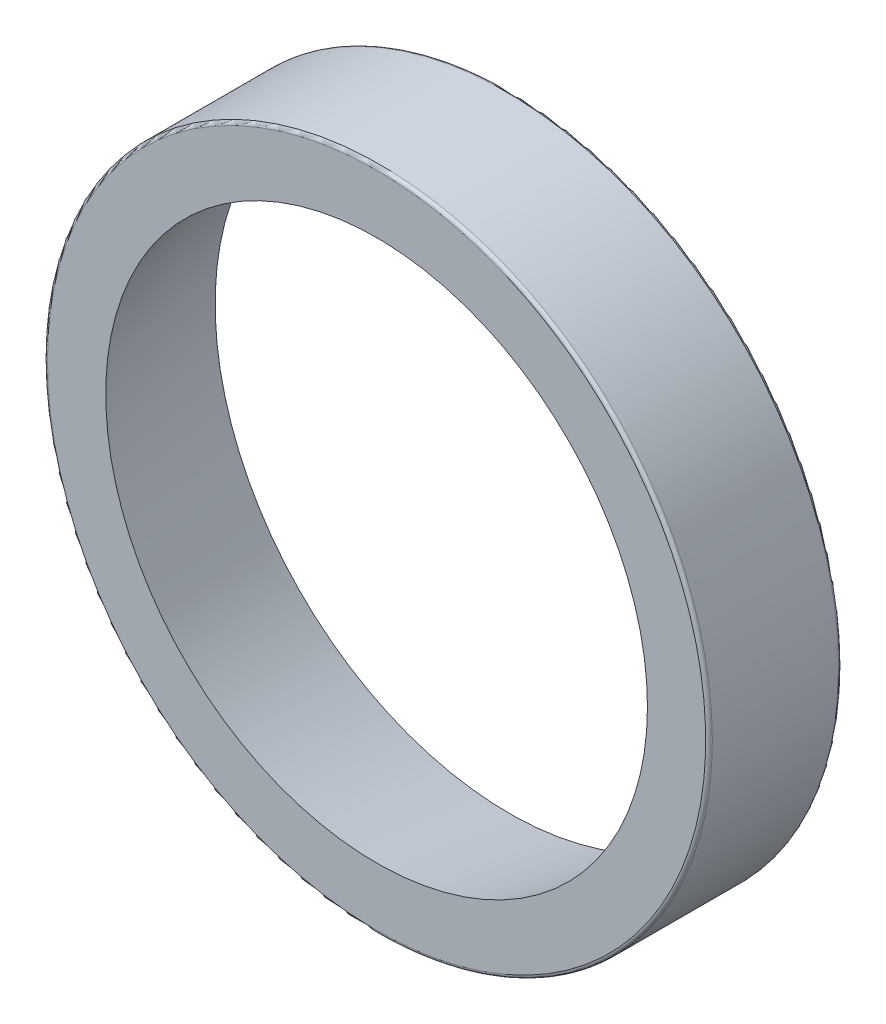
SolidWorks part; units mm, degrees
ref_plane "Front Plane" through (0, 0, 0) normal (0, 0, 1) x (1, 0, 0)
ref_plane "Top Plane" through (0, 0, 0) normal (0, 1, 0) x (1, 0, 0)
ref_plane "Right Plane" through (0, 0, 0) normal (1, 0, 0) x (0, 0, -1)
sketch "Sketch1" plane through (0, 0, 0) normal (1, 0, 0) x (0, 0, -1)
  line L0 (-8.3344, 0) -> (8.3344, 0) construction
  line L1 (0, 0) -> (0, 29.5656) construction
  line L2 (-8.3344, 15.875) -> (8.3344, 15.875) construction
  line L3 (8.3344, 15.875) -> (8.3344, 21.3512) construction
  line L4 (8.3344, 21.3512) -> (-8.3344, 18.4121) construction
  line L5 (-8.3344, 18.4121) -> (-8.3344, 15.875) construction
  line L7 (-8.3344, 29.5656) -> (3.4766, 29.5656)
  line L8 (3.4766, 29.5656) -> (3.4766, 26.172)
  line L9 (3.4766, 26.172) -> (-8.3344, 24.0894)
  line L10 (-8.3344, 24.0894) -> (-8.3344, 29.5656)
  line L11 (-8.3344, 24.0894) -> (-7.3635, 18.5833) construction
  line L12 (6.5698, 26.7174) -> (7.5406, 21.2113) construction
  line L14 (-8.3344, 18.4121) -> (-7.3635, 18.5833) construction
  line L15 (-8.3344, 18.4121) -> (7.5406, 21.2113) construction
  point P5 (0, 15.875)
  dimension "D1" = 100
  dimension "Width" = 16.6687
  dimension "OD" = 59.1312
  dimension "Shaft Dia" = 31.75
  dimension "D2" = 13.6906
  dimension "D3" = 5.4762
  dimension "Outer Wd" = 11.811
  dimension "Bearing Wd" = 15.875
revolve "Revolve1" add sketch "Sketch1" angle 360 about L0
sketch "Sketch5" plane through (0, 0, 0) normal (1, 0, 0) x (0, 0, -1)
  line L0 (8.3344, 21.3512) -> (-8.3344, 18.4121) construction
  line L1 (8.3344, 21.3512) -> (-8.3344, 18.4121)
  line L2 (-8.3344, 18.4121) -> (-8.3344, 15.875)
  line L3 (-8.3344, 15.875) -> (8.3344, 15.875)
  line L4 (8.3344, 15.875) -> (8.3344, 21.3512)
revolve "Revolve4" [suppressed] add sketch "Sketch5" angle 360 about L0
sketch "Sketch2" plane through (0, 0, 0) normal (1, 0, 0) x (0, 0, -1)
  line L0 (-8.3344, 23.3792) -> (-8.3344, 19.1222)
  line L1 (3.4766, 25.4618) -> (6.6912, 26.0286)
  line L2 (-8.3344, 19.1222) -> (3.4766, 21.2048)
  line L3 (6.5698, 26.7174) -> (7.5406, 21.2113) construction
  line L4 (3.4766, 21.2048) -> (3.4766, 25.4618) construction
  line L5 (3.4766, 25.4618) -> (-8.3344, 23.3792)
  line L6 (3.4766, 26.172) -> (-8.3344, 24.0894) construction
  line L7 (8.3344, 21.3512) -> (-8.3344, 18.4121) construction
  line L8 (-8.3344, 24.0894) -> (3.4766, 26.172) construction
  line L9 (-8.3344, 18.4121) -> (7.5406, 21.2113) construction
  line L10 (6.6912, 26.0286) -> (7.4192, 21.9)
  line L11 (-8.3344, 24.0894) -> (-8.3344, 23.3792) construction
  line L12 (-8.3344, 19.1222) -> (-8.3344, 18.4121) construction
  line L13 (3.4766, 29.5656) -> (3.4766, 26.172) construction
  line L14 (7.4192, 21.9) -> (3.4766, 21.2048)
  dimension "D1" = 5.591
  dimension "D2" = 4.1923
revolve "Revolve2" [suppressed] add sketch "Sketch2" angle 360 about L0
sketch "Sketch3" plane through (0, 0, 0) normal (1, 0, 0) x (0, 0, -1)
  line L0 (-8.3344, 21.2507) -> (3.4766, 23.3333) construction
  line L1 (-8.3344, 23.3792) -> (-8.3344, 19.1222) construction
  line L2 (3.4766, 21.2048) -> (3.4766, 25.4618) construction
  line L3 (-6.8781, 21.5075) -> (-7.3635, 24.2606)
  line L5 (-7.3635, 24.2606) -> (2.9912, 26.0864)
  line L6 (2.9912, 26.0864) -> (3.4766, 23.3333)
  line L7 (3.4766, 23.3333) -> (-6.8781, 21.5075)
  line L8 (3.4766, 26.172) -> (-8.3344, 24.0894) construction
  line L9 (-8.3344, 21.2507) -> (-7.8489, 21.3363) construction
  line L10 (-8.3344, 24.0894) -> (-7.3635, 18.5833) construction
  line L11 (-7.8489, 21.3363) -> (-7.3635, 21.4219) construction
  line L12 (-7.3635, 21.4219) -> (-6.8781, 21.5075) construction
revolve "Cut-Revolve1" [suppressed] cut sketch "Sketch3" angle 360 about L0
sketch "Sketch4" plane through (0, 0, 0) normal (1, 0, 0) x (0, 0, -1)
  line L0 (-7.3194, 24.0104) -> (3.0353, 25.8362)
  line L1 (3.0353, 25.8362) -> (3.4766, 23.3333)
  line L2 (3.4766, 23.3333) -> (-6.8781, 21.5075)
  line L3 (-8.3344, 21.2507) -> (-6.8781, 21.5075) construction
  line L4 (-6.8781, 21.5075) -> (-7.3194, 24.0104)
  line L6 (3.4766, 23.3333) -> (-6.8781, 21.5075) construction
  line L7 (3.4766, 26.172) -> (-8.3344, 24.0894) construction
  dimension "D1" = 0.254
revolve "Revolve3" [suppressed] add sketch "Sketch4" angle 360 about L0
ref_axis "Axis1" through (0, 0, -8.3344) along (0, 0, 1)
pattern_circular "CirPattern1" [suppressed] count 12 every 30 about axis through (0, 0, -8.3344) along (0, 0, 1) of bodies 402
pattern_circular "CirPattern2" [suppressed] count 12 every 30 about axis through (0, 0, -8.3344) along (0, 0, 1) of bodies 403
fillet "Fillet1" radius 0.2953 2 edges at (29.5656, 0, -3.4766) (29.5656, 0, 8.3344)
fillet "Fillet2" [suppressed] radius 0.2953
sketch "Sketch6" plane through (0, 0, 0) normal (1, 0, 0) x (0, 0, -1)
  line L0 (-51.8954, 29.5656) -> (-51.8954, 24.0894)
  line L1 (-51.8954, 24.0894) -> (-40.0844, 26.172)
  line L2 (-40.0844, 26.172) -> (-40.0844, 29.5656)
  line L3 (-40.0844, 29.5656) -> (-51.8954, 29.5656)
  line L4 (-8.3344, 29.5656) -> (3.4766, 29.5656) construction
  line L5 (-8.3344, 24.0894) -> (-8.3344, 29.5656) construction
  line L6 (3.4766, 29.5656) -> (3.4766, 26.172) construction
  line L8 (-8.3344, 29.2703) -> (-8.3344, -29.2703) construction
  dimension "D1" = 31.75
revolve "Revolve5" [suppressed] add sketch "Sketch6" angle 360 about L0
fillet "Fillet3" [suppressed] radius 0.2953
delete or keep bodies "Body-Delete1" [suppressed] type delete bodies bodies 399
equation "\"D3@Sketch1\" = \"D2@Sketch1\"/2.5"
equation "\"D2@Sketch2\" = \"D1@Sketch2\"*.75"
equation "\"Rollers@CirPattern2\" = \"OD@Sketch1\"*5"
equation "\"Angle@CirPattern2\" = 360/\"Rollers@CirPattern2\""
equation "\"D1@CirPattern1\" = \"Rollers@CirPattern2\""
equation "\"D2@CirPattern1\" = \"Angle@CirPattern2\""
equation "\"D1@Fillet1\" = \"Outer Wd@Sketch1\"*.025"
equation "\"D1@Fillet2\" = \"D1@Fillet1\""
equation "\"D1@Fillet3\" = \"D1@Fillet1\""
